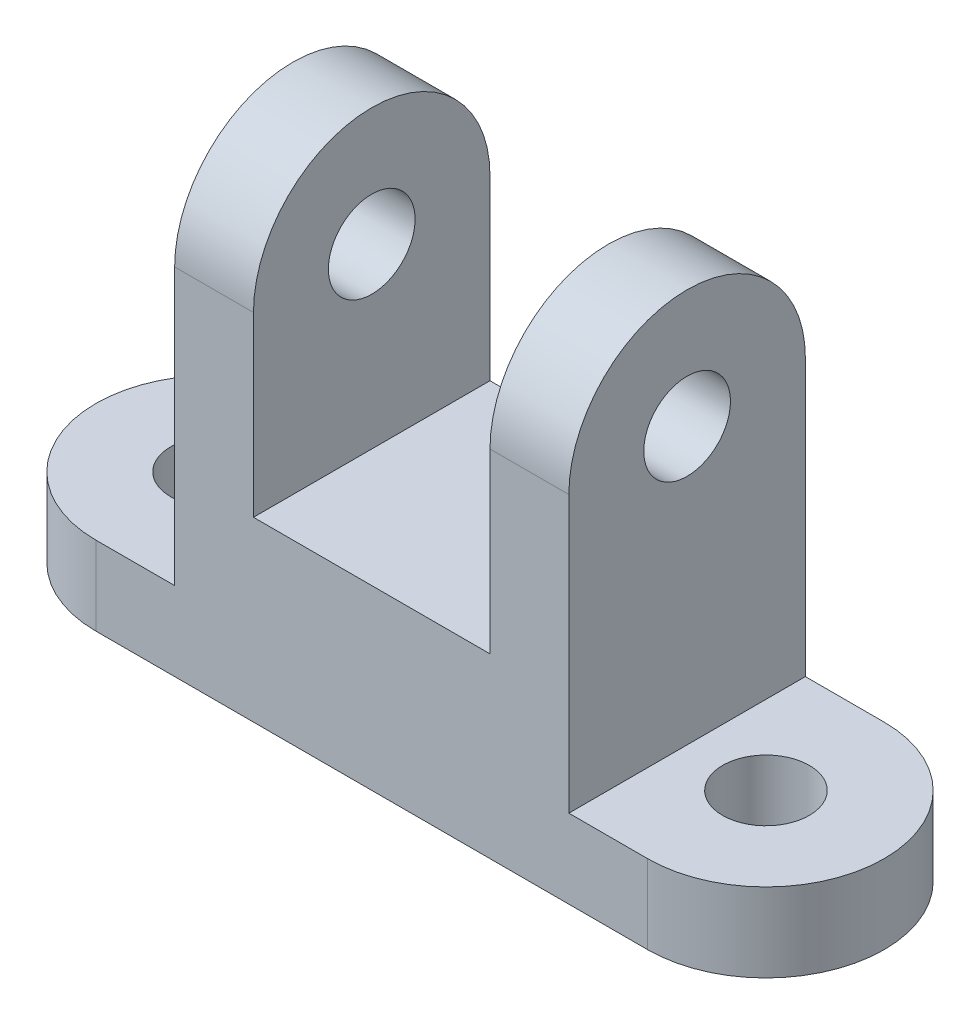
SolidWorks part; units mm, degrees
ref_plane "前视基准面" through (0, 0, 0) normal (0, 0, 1) x (1, 0, 0)
ref_plane "上视基准面" through (0, 0, 0) normal (0, 1, 0) x (1, 0, 0)
ref_plane "右视基准面" through (0, 0, 0) normal (1, 0, 0) x (0, 0, -1)
sketch "草图1" plane through (0, 0, 0) normal (0, 1, 0) x (1, 0, 0)
  line L0 (-7, 0) -> (7, 0) construction
  line L1 (-7, 3) -> (7, 3)
  line L2 (-7, -3) -> (7, -3)
  arc A0 (-7, 3) -> (-7, -3) centre (-7, 0) ccw
  arc A1 (7, -3) -> (7, 3) centre (7, 0) ccw
  point P2 (0, 0)
  dimension "D1" = 6
  dimension "D2" = 14
extrude "凸台-拉伸1" add sketch "草图1" along normal blind 2
sketch "草图2" plane through (0, 0, 0) normal (1, 0, 0) x (0, 0, -1)
  line L5 (-3, 0) -> (3, 0)
  line L6 (-3, 0) -> (-3, 12)
  line L7 (-3, 12) -> (3, 12)
  line L8 (3, 0) -> (3, 12)
  dimension "D1" = 12
  dimension "D2" = 6
extrude "凸台-拉伸2" add sketch "草图2" along normal mid plane 10
fillet "圆角1" 2 edges at (0, 12, -3) (0, 12, 3) type full round first side face at (0, 4, -3) second side face at (0, 4, 3) middle face at (0, 12, 0)
sketch "草图4" plane through (5, 0, 0) normal (1, 0, 0) x (0, 0, -1)
  circle A0 centre (0, 9) radius 1.1
  dimension "D1" = 2.2
extrude "切除-拉伸2" cut sketch "草图4" against normal blind 28
sketch "草图7" plane through (0, 2, 0) normal (0, 1, 0) x (1, 0, 0)
  circle A0 centre (7, 0) radius 1.1
  circle A1 centre (-7, 0) radius 1.1
  dimension "D1" = 2.2
  dimension "D2" = 2.2
extrude "切除-拉伸5" cut sketch "草图7" against normal blind 3.5
sketch "草图9" plane through (0, 0, 0) normal (0, -1, 0) x (1, 0, 0)
  circle A0 centre (0, 0) radius 1.5
  dimension "D1" = 3
extrude "切除-拉伸7" cut sketch "草图9" against normal blind 0.1
sketch "草图15" plane through (0, 0, -3) normal (0, 0, -1) x (-1, 0, 0)
  line L0 (0, 3.3) -> (0, -3.3) construction
  line L1 (-3, 13.7058) -> (3, 13.7058)
  line L2 (-3, 13.7058) -> (-3, 4.5)
  line L3 (-3, 4.5) -> (3, 4.5)
  line L4 (3, 13.7058) -> (3, 4.5)
  line L5 (-3, 13.7058) -> (3, 4.5) construction
  line L6 (-3, 4.5) -> (3, 13.7058) construction
  line L7 (5, 2) -> (7, 2) construction
  point P0 (0, 9.1029)
  dimension "D1" = 6
  dimension "D2" = 2.5
extrude "切除-拉伸8" cut sketch "草图15" against normal blind 10
